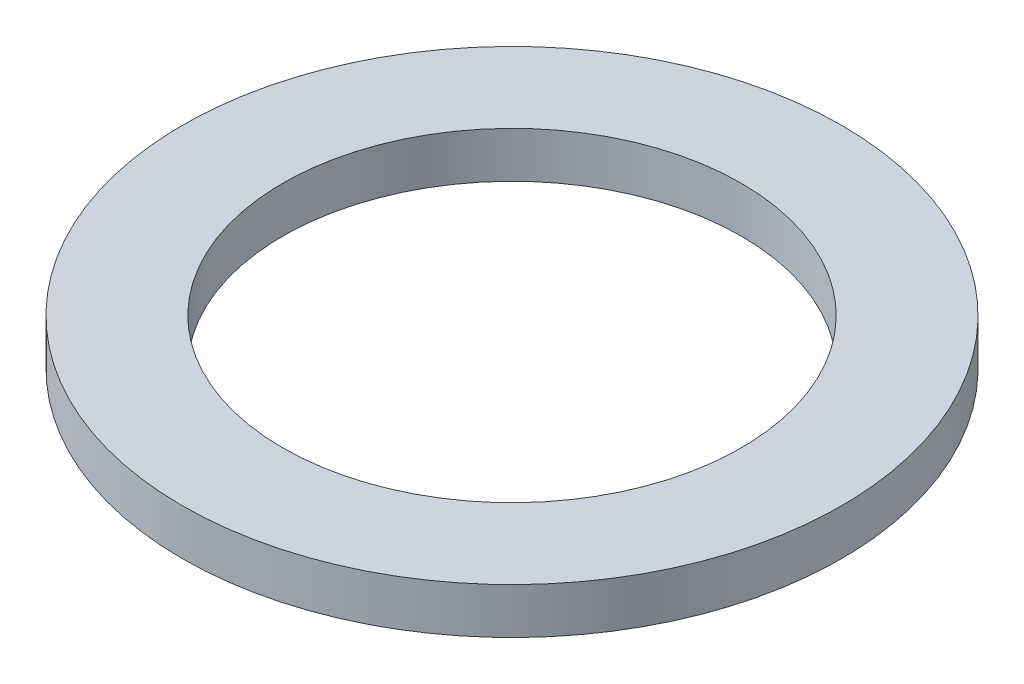
SolidWorks part; units mm, degrees
ref_plane "Front Plane" through (0, 0, 0) normal (0, 0, 1) x (1, 0, 0)
ref_plane "Top Plane" through (0, 0, 0) normal (0, 1, 0) x (1, 0, 0)
ref_plane "Right Plane" through (0, 0, 0) normal (1, 0, 0) x (0, 0, -1)
sketch "Sketch1" plane through (0, 0, 0) normal (0, 1, 0) x (1, 0, 0)
  circle A0 centre (0, 0) radius 57.5
  dimension "FLANGE_OD" = 115
extrude "Boss-Extrude1" add sketch "Sketch1" along normal blind 8
sketch "Sketch2" plane through (0, 0, 0) normal (0, 1, 0) x (1, 0, 0)
  circle A0 centre (0, 0) radius 40
  dimension "BORE_D" = 80
extrude "Cut-Extrude1" cut sketch "Sketch2" along normal through all
sketch "Sketch3" plane through (0, 8, 0) normal (0, 1, 0) x (1, 0, 0)
  circle A0 centre (0, 0) radius 22.3555 construction
  circle A1 centre (-22.3555, 0) radius 2.0317
  dimension "BOLT_D" = 4.0634
  dimension "BOLT_PCD" = 44.7109
extrude "Cut-Extrude2" cut sketch "Sketch3" against normal blind 6.8934 rebuild error yes
pattern_circular "CirPattern1" count 4 over 360 rebuild error yes
